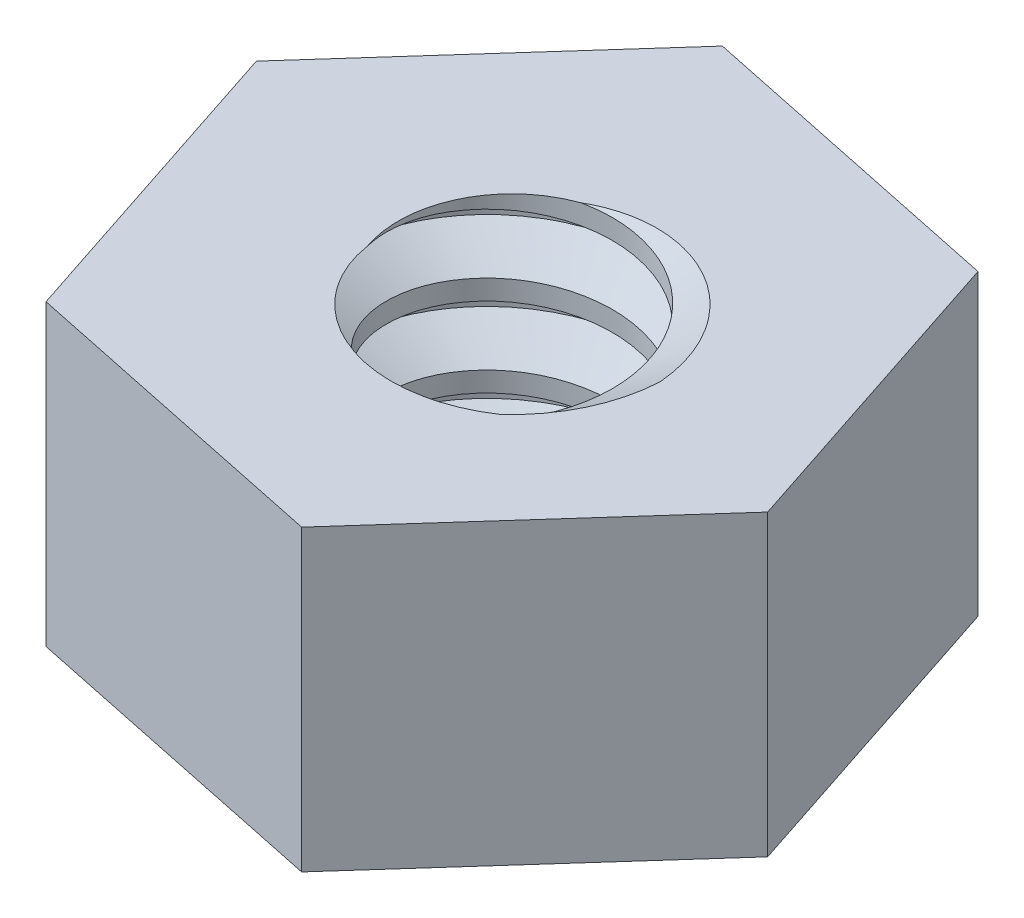
SolidWorks part; units mm, degrees
ref_plane "Front Plane" through (0, 0, 0) normal (0, 0, 1) x (1, 0, 0)
ref_plane "Top Plane" through (0, 0, 0) normal (0, 1, 0) x (1, 0, 0)
ref_plane "Right Plane" through (0, 0, 0) normal (1, 0, 0) x (0, 0, -1)
sketch "Sketch1" plane through (0, 0, 0) normal (0, 1, 0) x (1, 0, 0)
  line L0 (-90.4875, 0) -> (0, 0) construction
  line L14 (7.0152, 7.8492) -> (-3.29, 10)
  line L15 (-3.29, 10) -> (-10.3053, 2.1508)
  line L16 (-10.3053, 2.1508) -> (-7.0152, -7.8492)
  line L17 (-7.0152, -7.8492) -> (3.29, -10)
  line L18 (3.29, -10) -> (10.3053, -2.1508)
  line L19 (10.3053, -2.1508) -> (7.0152, 7.8492)
  circle A3 centre (0, 0) radius 5
  circle A6 centre (0, 0) radius 9.1169 construction
  dimension "D11" = 10
extrude "Boss-Extrude1" add sketch "Sketch1" along normal blind 9.525 contours A3 region at (8.3874, 0, -2.7595)
sketch "Sketch5" plane through (0, 9.525, 0) normal (0, 1, 0) x (1, 0, 0)
  circle A0 centre (0, 0) radius 5 construction
  circle A1 centre (0, 0) radius 5
thread "Thread1" pitch 2.54 method extrude profile "Thread Profile1" start angle 3, offset 3.81, length 15.08, pitch 2.54, diameter 10
ref_plane "Plane1" through (-4.9931, 13.335, -0.2617) normal (-0.0523, 0, 0.9986) x (-0.9986, 0, -0.0523)
sketch "Thread Profile1" plane through (-4.9931, 13.335, -0.2617) normal (-0.0523, 0, 0.9986) x (-0.9986, 0, -0.0523)
  line L0 (0, 0) -> (0, 2.54) construction
  line L11 (0, 0) -> (0, 2.2225)
  line L12 (0, 2.2225) -> (-1.3748, 1.4287)
  line L13 (-1.3748, 1.4287) -> (-1.3748, 0.7937)
  line L15 (-1.3748, 0.7937) -> (0, 0)
  line L17 (-1.3748, 1.1112) -> (0, 1.1112) construction
  point P2 (0, 0)
  dimension "Pitch" = 2.54
  dimension "Profile_Angle" = 60
  dimension "Profile_Land" = 0.635
  dimension "Profile_Height" = 1.3748
sketch "Sketch25" plane through (8.6603, 0, -2.8492) normal (0.9499, 0, -0.3125) x (-0.3125, 0, -0.9499)
  line L0 (-5.2637, 9.525) -> (5.2637, 9.525) construction
  line L1 (-5.2637, 9.525) -> (5.2637, 9.525)
  line L2 (-5.2637, 0) -> (5.2637, 0) construction
  line L3 (-5.2637, 0) -> (5.2637, 0)
  line L4 (-5.2637, 0) -> (-5.2637, -5.0697)
  line L5 (-5.2637, -5.0697) -> (5.2637, -5.0697)
  line L6 (5.2637, -5.0697) -> (5.2637, 0)
  line L7 (-5.2637, 9.525) -> (-5.2637, 16.5179)
  line L8 (-5.2637, 16.5179) -> (5.2637, 16.5179)
  line L9 (5.2637, 16.5179) -> (5.2637, 9.525)
extrude "Cut-Extrude1" cut sketch "Sketch25" against normal through all
